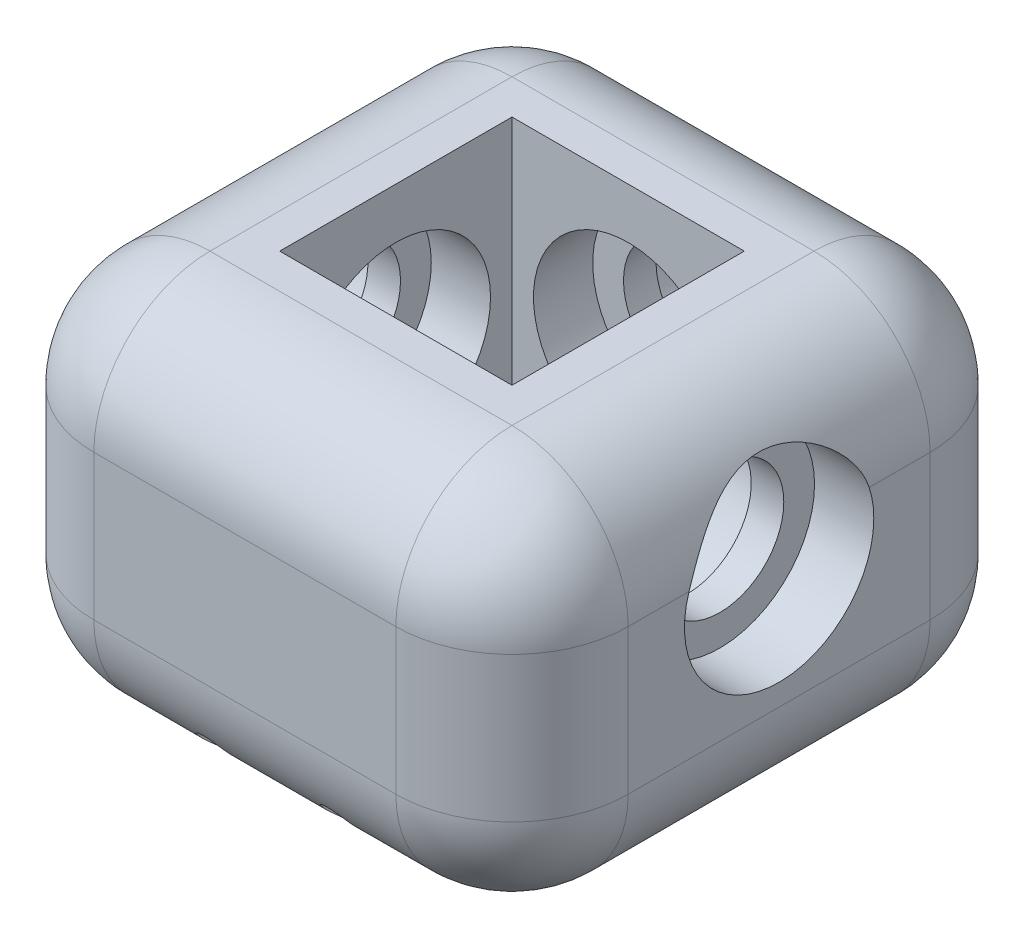
SolidWorks part; units mm, degrees
ref_plane "Front Plane" through (0, 0, 0) normal (0, 0, 1) x (1, 0, 0)
ref_plane "Top Plane" through (0, 0, 0) normal (0, 1, 0) x (1, 0, 0)
ref_plane "Right Plane" through (0, 0, 0) normal (1, 0, 0) x (0, 0, -1)
sketch "Sketch1" plane through (0, 0, 0) normal (0, 1, 0) x (1, 0, 0)
  line L6 (10, 10) -> (-10, 10)
  line L7 (10, 10) -> (10, -10)
  line L8 (10, -10) -> (-10, -10)
  line L9 (-10, 10) -> (-10, -10)
  line L10 (10, 10) -> (-10, -10) construction
  line L11 (10, -10) -> (-10, 10) construction
  line L12 (23, 23) -> (-23, 23)
  line L13 (23, 23) -> (23, -23)
  line L14 (23, -23) -> (-23, -23)
  line L15 (-23, 23) -> (-23, -23)
  line L16 (23, 23) -> (-23, -23) construction
  line L17 (23, -23) -> (-23, 23) construction
  point P0 (0, 0)
  point P5 (0, 0)
  dimension "D1" = 20
  dimension "D2" = 20
  dimension "D3" = 46
  dimension "D4" = 46
extrude "Boss-Extrude1" add sketch "Sketch1" along normal blind 12.5 and the other way blind 20
sketch "Sketch2" plane through (-23, 0, 0) normal (-1, 0, 0) x (0, 0, 1)
  circle A0 centre (0, 0) radius 8.15
  dimension "D1" = 16.3
extrude "Cut-Extrude1" cut sketch "Sketch2" against normal blind 5.1
sketch "Sketch3" plane through (-10, 0, 0) normal (1, 0, 0) x (0, 0, -1)
  circle A0 centre (0, 0) radius 8.15
  circle A1 centre (0, 0) radius 8.15 construction
  dimension "D1" = 0
extrude "Cut-Extrude2" cut sketch "Sketch3" against normal blind 5.1
sketch "Sketch4" plane through (-17.9, 0, 0) normal (-1, 0, 0) x (0, 0, 1)
  circle A0 centre (0, 0) radius 5.5
  dimension "D1" = 11
extrude "Cut-Extrude3" cut sketch "Sketch4" against normal blind 100
sketch "Sketch5" plane through (10, 0, 0) normal (-1, 0, 0) x (0, 0, 1)
  circle A0 centre (0, 0) radius 8.15
  circle A1 centre (0, 0) radius 8.15 construction
  dimension "D1" = 0
extrude "Cut-Extrude4" cut sketch "Sketch5" against normal blind 5.1
sketch "Sketch6" plane through (23, 0, 0) normal (1, 0, 0) x (0, 0, -1)
  circle A0 centre (0, 0) radius 8.15
  circle A1 centre (0, 0) radius 8.15 construction
  dimension "D1" = 0
extrude "Cut-Extrude5" cut sketch "Sketch6" against normal blind 5.1
sketch "Sketch7" plane through (0, 0, -23) normal (0, 0, -1) x (-1, 0, 0)
  circle A0 centre (0, 0) radius 8.15
  dimension "D1" = 16.3
extrude "Cut-Extrude6" cut sketch "Sketch7" against normal blind 5.1
sketch "Sketch8" plane through (0, 0, -10) normal (0, 0, 1) x (1, 0, 0)
  circle A0 centre (0, 0) radius 8.15
  circle A1 centre (0, 0) radius 8.15 construction
  dimension "D1" = 0
extrude "Cut-Extrude7" cut sketch "Sketch8" against normal blind 5.1
sketch "Sketch9" plane through (0, 0, -17.9) normal (0, 0, -1) x (-1, 0, 0)
  circle A0 centre (0, 0) radius 5.5
  dimension "D1" = 11
extrude "Cut-Extrude8" cut sketch "Sketch9" against normal blind 5.1
fillet "Fillet1" radius 10 12 edges at (23, -20, 0) (23, 12.5, 0) (23, -3.75, 23) (0, -20, 23) (0, 12.5, 23) (-23, -3.75, 23) (-23, -20, 0) (-23, 12.5, 0) (23, -3.75, -23) (-23, -3.75, -23) (0, -20, -23) (0, 12.5, -23)
sketch "Sketch11" plane through (0, 0, 10) normal (0, 0, -1) x (-1, 0, 0)
  line L1 (7.5, -12.5) -> (-7.5, -12.5)
  line L2 (7.5, -12.5) -> (7.5, -20)
  line L3 (7.5, -20) -> (-7.5, -20)
  line L4 (-7.5, -12.5) -> (-7.5, -20)
  line L5 (7.5, -12.5) -> (-7.5, -20) construction
  line L6 (7.5, -20) -> (-7.5, -12.5) construction
  line L8 (10, -20) -> (-10, -20) construction
  point P0 (-7.7531, -12.3735)
  point P10 (0, -16.25)
  dimension "D1" = 0
  dimension "D2" = 10
  dimension "D3" = 15
  dimension "D4" = 7.5
extrude "Boss-Extrude2" add sketch "Sketch11" along normal blind 6
sketch "Sketch10" plane through (0, 0, 4) normal (0, 0, -1) x (-1, 0, 0)
  line L0 (10, -20) -> (7.5, -20) construction
  circle A0 centre (5.345, -17) radius 1.3
  circle A1 centre (-5.335, -17) radius 1.3
  dimension "D4" = 2.6
  dimension "D5" = 2.6
  dimension "D1" = 3
  dimension "D2" = 10.68
  dimension "D3" = 4.655
  dimension "D6" = 0
extrude "Cut-Extrude9" cut sketch "Sketch10" against normal blind 100
fillet "Fillet2" radius 5 3 edges at (0, -12.5, 10) (-7.5, -16.25, 10) (7.5, -16.25, 10)
